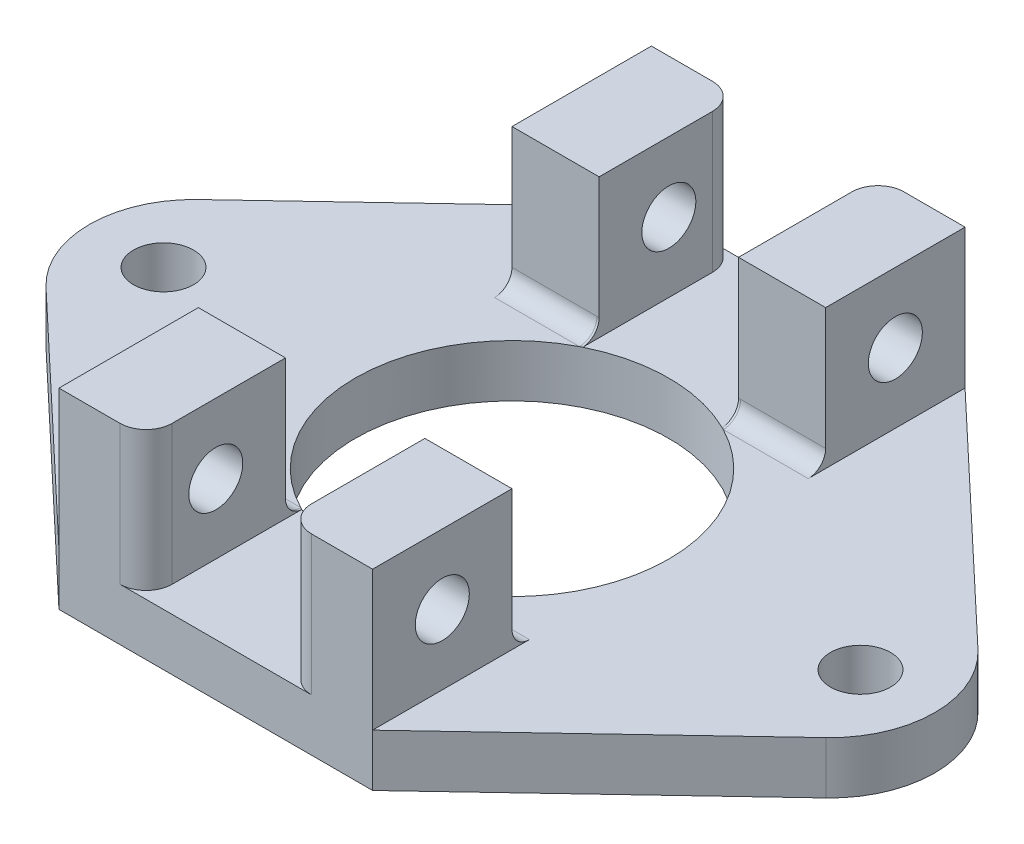
SolidWorks part; units mm, degrees
material "ABS"
ref_plane "前视基准面" through (0, 0, 0) normal (0, 0, 1) x (1, 0, 0)
ref_plane "上视基准面" through (0, 0, 0) normal (0, 1, 0) x (1, 0, 0)
ref_plane "右视基准面" through (0, 0, 0) normal (1, 0, 0) x (0, 0, -1)
sketch "草图1" plane through (0, 0, 0) normal (0, 1, 0) x (1, 0, 0)
  line L0 (-22.5, 0) -> (22.5, 0) construction
  line L1 (-22.5, -17) -> (22.5, -17)
  line L2 (-22.5, -17) -> (-22.5, 17)
  line L3 (-22.5, 17) -> (22.5, 17)
  line L4 (22.5, -17) -> (22.5, 17)
  line L5 (-22.5, -17) -> (22.5, 17) construction
  line L6 (-22.5, 17) -> (22.5, -17) construction
  line L7 (-22.5, 17) -> (-9, 17)
  line L8 (-22.5, 17) -> (-22.5, 6.8)
  line L9 (-22.5, 6.8) -> (-9, 6.8)
  line L10 (-9, 17) -> (-9, 6.8)
  line L11 (-22.5, 17) -> (-9, 6.8) construction
  line L12 (-22.5, 6.8) -> (-9, 17) construction
  line L13 (22.5, 17) -> (9, 17)
  line L14 (22.5, 17) -> (22.5, 6.8)
  line L15 (22.5, 6.8) -> (9, 6.8)
  line L16 (9, 17) -> (9, 6.8)
  line L17 (22.5, 17) -> (9, 6.8) construction
  line L18 (22.5, 6.8) -> (9, 17) construction
  line L19 (22.5, -17) -> (9, -17)
  line L20 (22.5, -17) -> (22.5, -6.8)
  line L21 (22.5, -6.8) -> (9, -6.8)
  line L22 (9, -17) -> (9, -6.8)
  line L23 (22.5, -17) -> (9, -6.8) construction
  line L24 (22.5, -6.8) -> (9, -17) construction
  line L25 (-22.5, -17) -> (-9, -17)
  line L26 (-22.5, -17) -> (-22.5, -6.8)
  line L27 (-22.5, -6.8) -> (-9, -6.8)
  line L28 (-9, -17) -> (-9, -6.8)
  line L29 (-22.5, -17) -> (-9, -6.8) construction
  line L30 (-22.5, -6.8) -> (-9, -17) construction
  line L31 (0, 17) -> (0, -17) construction
  line L32 (-22.5, 0) -> (-17.5, 0) construction
  line L33 (-22.5, 0) -> (-22.5, 3.5) construction
  line L34 (-22.5, 3.5) -> (-17.5, 3.5) construction
  line L35 (-17.5, 0) -> (-17.5, 3.5) construction
  line L36 (-22.5, 0) -> (-17.5, 3.5) construction
  line L37 (-22.5, 3.5) -> (-17.5, 0) construction
  circle A0 centre (0, 0) radius 9
  circle A1 centre (-17.5, 3.5) radius 1.55
  circle A2 centre (-17.5, -3.5) radius 1.55
  circle A3 centre (17.5, -3.5) radius 1.55
  circle A4 centre (17.5, 3.5) radius 1.55
  point P10 (-15.75, 11.9)
  point P14 (15.75, 11.9)
  point P18 (15.75, -11.9)
  point P22 (-15.75, -11.9)
  point P28 (-20, 1.75)
  dimension "D1" = 18
  dimension "D10" = 3.1
  dimension "D2" = 45
  dimension "D3" = 34
  dimension "D4" = 13.5
  dimension "D5" = 13.5
  dimension "D6" = 13.5
  dimension "D7" = 13.5
  dimension "D8" = 5
  dimension "D9" = 3.5
extrude "凸台-拉伸1" add sketch "草图1" along normal blind 3 contours L28 L1 L22 L21 L4 L15 L16 L3 L10 L9 L2 L27 A0 region at (-8.436, 0, 11.9)
sketch "草图2" plane through (0, 3, 0) normal (0, 1, 0) x (1, 0, 0)
  line L1 (-9, 17) -> (-4, 17)
  line L2 (-9, 17) -> (-9, 9)
  line L3 (-9, 9) -> (-4, 9)
  line L4 (-4, 17) -> (-4, 9)
  line L5 (-9, 17) -> (-4, 9) construction
  line L6 (-9, 9) -> (-4, 17) construction
  line L7 (9, 17) -> (4, 17)
  line L8 (9, 17) -> (9, 9)
  line L9 (9, 9) -> (4, 9)
  line L10 (4, 17) -> (4, 9)
  line L11 (9, 17) -> (4, 9) construction
  line L12 (9, 9) -> (4, 17) construction
  line L13 (-9, -17) -> (-4, -17)
  line L14 (-9, -17) -> (-9, -9)
  line L15 (-9, -9) -> (-4, -9)
  line L16 (-4, -17) -> (-4, -9)
  line L17 (-9, -17) -> (-4, -9) construction
  line L18 (-9, -9) -> (-4, -17) construction
  line L19 (9, -17) -> (4, -17)
  line L20 (9, -17) -> (9, -9)
  line L21 (9, -9) -> (4, -9)
  line L22 (4, -17) -> (4, -9)
  line L23 (9, -17) -> (4, -9) construction
  line L24 (9, -9) -> (4, -17) construction
  point P4 (-6.5, 13)
  point P10 (6.5, 13)
  point P16 (-6.5, -13)
  point P22 (6.5, -13)
  dimension "D1" = 8
  dimension "D2" = 5
  dimension "D3" = 5
  dimension "D4" = 5
  dimension "D5" = 5
  dimension "D6" = 8
  dimension "D7" = 8
extrude "凸台-拉伸2" add sketch "草图2" along normal blind 8
sketch "草图3" plane through (-9, 0, 0) normal (-1, 0, 0) x (0, 0, 1)
  line L0 (0, 0) -> (0, 3) construction
  line L1 (-17, 11) -> (-9, 11) construction
  line L2 (-17, 11) -> (-17, 3) construction
  line L3 (-17, 3) -> (-9, 3) construction
  line L4 (-9, 11) -> (-9, 3) construction
  line L5 (-17, 11) -> (-9, 3) construction
  line L6 (-17, 3) -> (-9, 11) construction
  line L7 (6.8, 3) -> (-6.8, 3) construction
  circle A0 centre (-13, 7) radius 1.55
  circle A1 centre (13, 7) radius 1.55
  point P4 (-13, 7)
  dimension "D1" = 3.1
extrude "切除-拉伸1" cut sketch "草图3" against normal blind 18
sketch "草图6" plane through (0, 3, 0) normal (0, 1, 0) x (1, 0, 0)
  line L0 (9, -6.8) -> (9, 6.8)
  line L1 (9, 6.8) -> (22.5, 6.8)
  line L2 (22.5, 6.8) -> (22.5, -6.8)
  line L3 (22.5, -6.8) -> (9, -6.8)
  line L4 (-9, -6.8) -> (-22.5, -6.8)
  line L5 (-22.5, -6.8) -> (-22.5, 6.8)
  line L6 (-22.5, 6.8) -> (-9, 6.8)
  line L7 (-9, 9) -> (-9, 6.8) construction
  line L8 (-22.5, 6.8) -> (-9, 6.8) construction
  line L9 (-9, 6.8) -> (-9, -6.8)
extrude "切除-拉伸3" cut sketch "草图6" against normal blind 10
sketch "草图7" plane through (0, 0, 0) normal (0, 1, 0) x (1, 0, 0)
  line L0 (9, -17) -> (27, 0)
  line L1 (27, 0) -> (9, 17)
  line L2 (27, 0) -> (0, 0) construction
  line L3 (0, 0) -> (0, 17) construction
  line L4 (-4, 17) -> (4, 17) construction
  line L5 (-27, 0) -> (-9, 17)
  line L6 (-9, -17) -> (-27, 0)
  line L7 (9, 9) -> (9, 17) construction
  line L8 (-9, 17) -> (-9, -17)
  line L9 (9, 17) -> (9, -17)
  circle A0 centre (20, 0) radius 1.725
  circle A1 centre (-20, 0) radius 1.725
  dimension "D3" = 3.45
  dimension "D1" = 18
  dimension "D2" = 20
extrude "凸台-拉伸4" add sketch "草图7" along normal up to surface (3 mm away) up to face at (0, 3, -9.875)
fillet "圆角1" radius 6 2 edges at (27, 1.5, 0) (-27, 1.5, 0)
fillet "圆角2" radius 1 4 edges at (6.5, 3, 9) (-6.5, 3, 9) (6.5, 3, -9) (-6.5, 3, -9)
fillet "圆角6" radius 1.5 4 edges at (4, 7, -17) (-4, 7, -17) (-4, 7, 17) (4, 7, 17)
